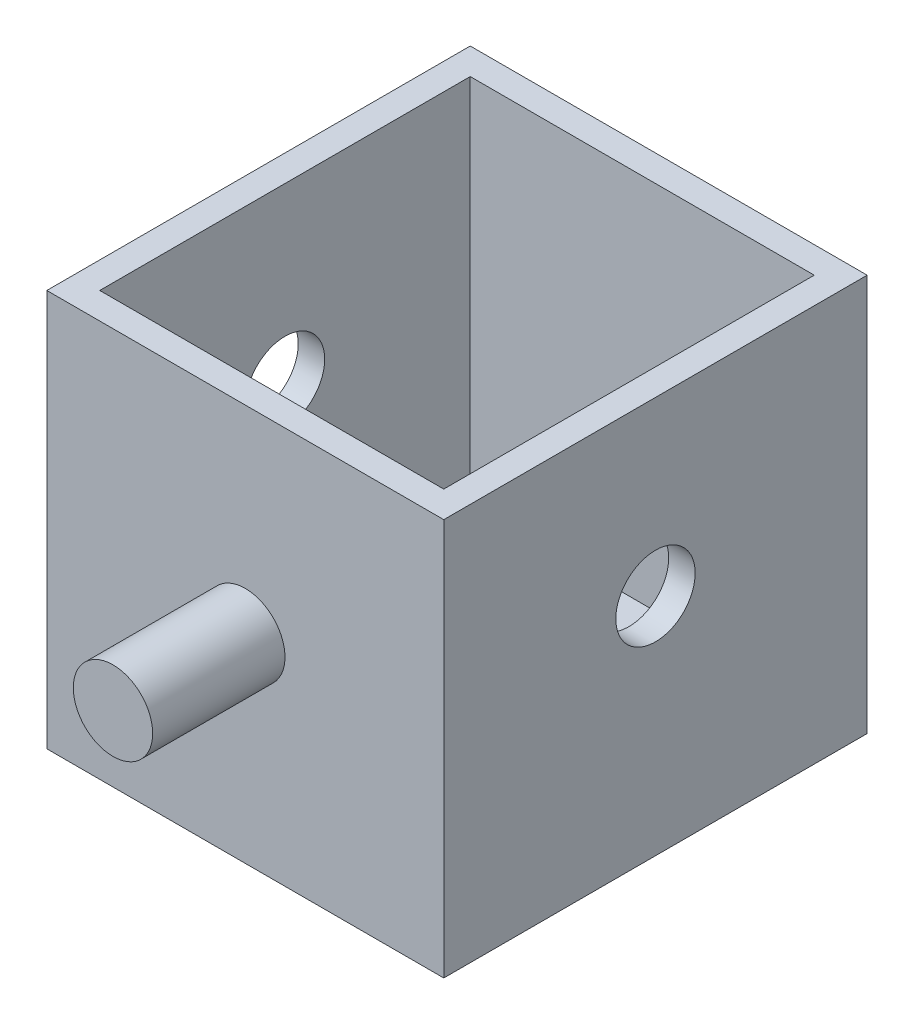
SolidWorks part; units mm, degrees
ref_plane "Front Plane" through (0, 0, 0) normal (0, 0, 1) x (1, 0, 0)
ref_plane "Top Plane" through (0, 0, 0) normal (0, 1, 0) x (1, 0, 0)
ref_plane "Right Plane" through (0, 0, 0) normal (1, 0, 0) x (0, 0, -1)
sketch "Sketch1" plane through (0, 0, 0) normal (0, 0, 1) x (1, 0, 0)
  line L1 (-19.05, -19.05) -> (19.05, -19.05)
  line L2 (-19.05, -19.05) -> (-19.05, 19.05)
  line L3 (-19.05, 19.05) -> (19.05, 19.05)
  line L4 (19.05, -19.05) -> (19.05, 19.05)
  line L5 (-19.05, -19.05) -> (19.05, 19.05) construction
  line L6 (-19.05, 19.05) -> (19.05, -19.05) construction
  point P0 (0, 0)
  dimension "D1" = 38.1
  dimension "D2" = 38.1
extrude "main body" add sketch "Sketch1" along normal blind 40.64
shell "hollow it" thickness 2.54 removed face at (0, 19.05, 20.32)
ref_point "cut point"
sketch "Sketch2" plane through (19.05, 0, 0) normal (1, 0, 0) x (0, 0, -1)
  line L0 (-40.64, -19.05) -> (0, -19.05) construction
  circle A0 centre (-20.32, 2.54) radius 3.81
  point P3 (-20.32, -19.05)
  dimension "D1" = 21.59
  dimension "D2" = 20.32
ref_point "bigger nibble point"
ref_point "bigger nibble here, too"
sketch "Sketch3" plane through (0, 0, 40.64) normal (0, 0, 1) x (1, 0, 0)
  circle A0 centre (0, 0) radius 3.81
  dimension "D1" = 7.62
extrude "nibble no 1" add sketch "Sketch3" along normal blind 12.7
sketch "Sketch4" plane through (0, 0, 0) normal (0, 0, -1) x (-1, 0, 0)
  circle A0 centre (0, 0) radius 3.81
  dimension "D1" = 7.62
extrude "nibble no 2" add sketch "Sketch4" along normal blind 12.7
ref_point "nibble center"
ref_plane "nibble flag plane" through (0, 0, 0) normal (0, -1, 0) x (-1, 0, 0)
sketch "Sketch5" plane through (0, 0, 0) normal (0, -1, 0) x (-1, 0, 0)
  line L1 (-0.8217, 4.4483) -> (0.4483, 4.4483)
  line L2 (-0.8217, 4.4483) -> (-0.8217, 8.2583)
  line L3 (-0.8217, 8.2583) -> (0.4483, 8.2583)
  line L4 (0.4483, 4.4483) -> (0.4483, 8.2583)
  line L5 (-0.8217, 4.4483) -> (0.4483, 8.2583) construction
  line L6 (-0.8217, 8.2583) -> (0.4483, 4.4483) construction
  point P0 (-0.1867, 6.3533)
  dimension "D1" = 1.27
  dimension "D2" = 3.81
extrude "flag" add sketch "Sketch5" along normal blind 0.254
extrude "nibble holes" cut sketch "Sketch2" against normal through all
